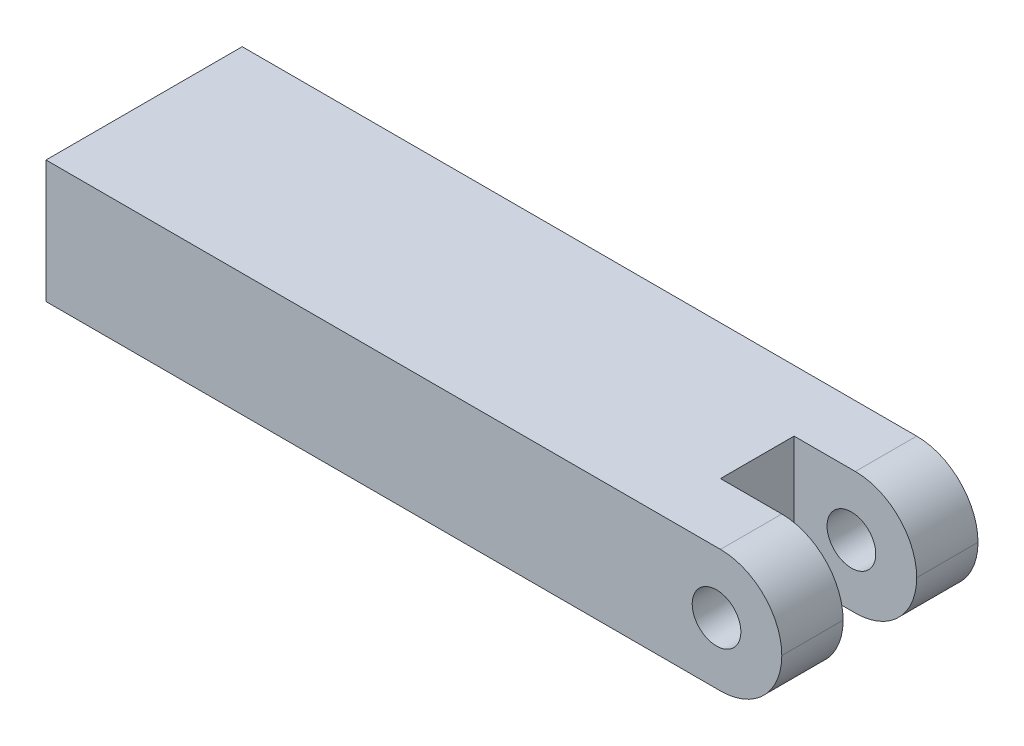
SolidWorks part; units mm, degrees
ref_plane "Plan de face" through (0, 0, 0) normal (0, 0, 1) x (1, 0, 0)
ref_plane "Plan de dessus" through (0, 0, 0) normal (0, 1, 0) x (1, 0, 0)
ref_plane "Plan de droite" through (0, 0, 0) normal (1, 0, 0) x (0, 0, -1)
sketch "Esquisse2" plane through (0, 0, 0) normal (0, 0, 1) x (1, 0, 0)
  line L6 (50, 10) -> (-50, 10)
  line L9 (50, 10) -> (50, -10)
  line L10 (50, -10) -> (-50, -10)
  line L11 (-50, 10) -> (-50, -10)
  line L12 (50, 10) -> (-50, -10) construction
  line L13 (50, -10) -> (-50, 10) construction
  point P0 (0, 0)
  dimension "D1" = 100
  dimension "D2" = 20
extrude "Boss.-Extru.1" add sketch "Esquisse2" along normal blind 32
sketch "Esquisse6" plane through (50, 0, 0) normal (1, 0, 0) x (0, 0, -1)
  line L0 (-32, -10) -> (0, -10) construction
  line L1 (-32, 10) -> (-22, 10)
  line L2 (-32, 10) -> (-32, -10)
  line L3 (-32, -10) -> (-22, -10)
  line L4 (-22, 10) -> (-22, -10)
  line L7 (-32, 10) -> (0, 10) construction
  line L8 (-16, 10) -> (-16, -10) construction
  line L9 (0, -10) -> (-10, -10)
  line L10 (-10, 10) -> (-10, -10)
  line L11 (0, 10) -> (-10, 10)
  line L12 (0, 10) -> (0, -10)
  dimension "D1" = 10
extrude "Boss.-Extru.3" add sketch "Esquisse6" along normal blind 20
fillet "Congé2" radius 10 4 edges at (70, -10, 27) (70, -10, 5) (70, 10, 5) (70, 10, 27)
sketch "Esquisse7" plane through (0, 0, 0) normal (0, 0, -1) x (-1, 0, 0)
  circle A0 centre (-59.3542, 0) radius 3.9687
  dimension "D1" = 7.9375
extrude "Enlèv. mat.-Extru.1" cut sketch "Esquisse7" against normal through all
